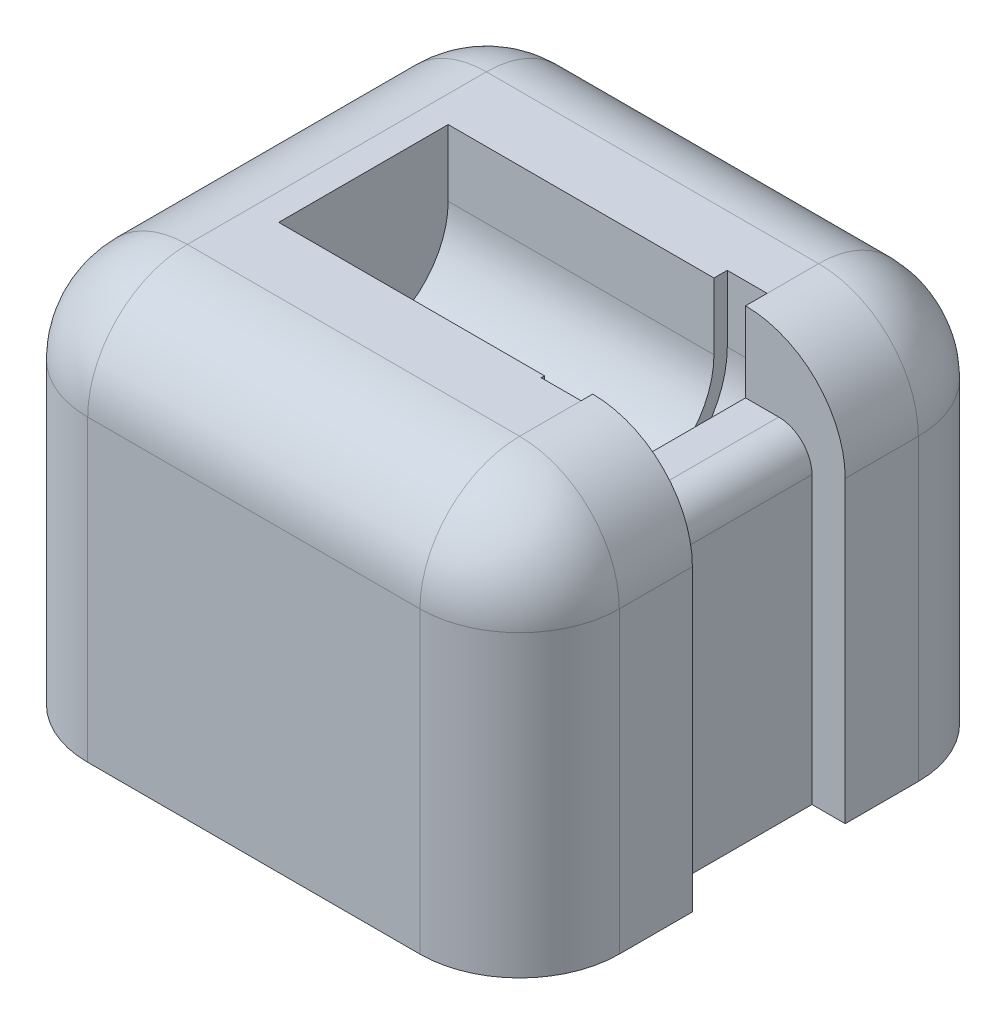
SolidWorks part; units mm, degrees
ref_plane "Front Plane" through (0, 0, 0) normal (0, 0, 1) x (1, 0, 0)
ref_plane "Top Plane" through (0, 0, 0) normal (0, 1, 0) x (1, 0, 0)
ref_plane "Right Plane" through (0, 0, 0) normal (1, 0, 0) x (0, 0, -1)
sketch "Sketch1" plane through (0, 0, 0) normal (0, 1, 0) x (1, 0, 0)
  line L1 (7.5, -7.5) -> (-7.5, -7.5)
  line L2 (7.5, -7.5) -> (7.5, 7.5)
  line L3 (7.5, 7.5) -> (-7.5, 7.5)
  line L4 (-7.5, -7.5) -> (-7.5, 7.5)
  line L5 (7.5, -7.5) -> (-7.5, 7.5) construction
  line L6 (7.5, 7.5) -> (-7.5, -7.5) construction
  point P0 (0, 0)
  dimension "D1" = 15
  dimension "D2" = 15
extrude "Boss-Extrude1" add sketch "Sketch1" along normal blind 12
sketch "Sketch2" plane through (7.5, 0, 0) normal (1, 0, 0) x (0, 0, -1)
  line L2 (2.3, 10.4) -> (2.3, 9.6)
  line L3 (2.3, 9.6) -> (-2.3, 9.6)
  line L4 (-2.3, 10.4) -> (-2.3, 9.6)
  line L5 (2.3, 10.4) -> (-2.3, 9.6) construction
  line L6 (2.3, 9.6) -> (-2.3, 10.4) construction
  line L7 (-7.5, 12) -> (7.5, 12) construction
  line L9 (-2.3, 10.4) -> (-2.3, 12)
  line L10 (-2.3, 12) -> (2.3, 12)
  line L11 (2.3, 10.4) -> (2.3, 12)
  point P0 (0, 10)
  point P9 (-1.3001, 10.2334)
  point P11 (2.1985, 10.3824)
  point P14 (0, 10)
  point P15 (-2.4019, 9.6178)
  point P16 (0, 0)
  dimension "D1" = 10
  dimension "D2" = 0.8
  dimension "D3" = 4.6
extrude "Cut-Extrude1" cut sketch "Sketch2" against normal blind 2
sketch "Sketch3" plane through (5.5, 0, 0) normal (1, 0, 0) x (0, 0, -1)
  line L0 (-2.65, 11.2961) -> (-2.65, 8.7039)
  line L1 (-2.65, 10) -> (2.95, 10) construction
  line L2 (-2.65, 11.2961) -> (-2.65, 12)
  line L3 (-7.5, 12) -> (-2.3, 12) construction
  line L4 (-2.65, 12) -> (2.95, 12)
  line L5 (2.95, 12) -> (2.95, 10)
  arc A0 (-2.65, 8.7039) -> (2.95, 10) centre (0, 10) ccw
  dimension "D1" = 5.9
  dimension "D2" = 5.6
extrude "Cut-Extrude2" cut sketch "Sketch3" against normal blind 1.2
sketch "Sketch4" plane through (4.3, 0, 0) normal (1, 0, 0) x (0, 0, -1)
  line L0 (-2.55, 10) -> (-2.55, 12)
  line L1 (2.95, 12) -> (-2.65, 12) construction
  line L2 (-2.55, 12) -> (2.55, 12)
  line L3 (2.55, 12) -> (2.55, 10)
  arc A0 (-2.55, 10) -> (2.55, 10) centre (0, 10) ccw
  dimension "D1" = 5.1
extrude "Cut-Extrude3" cut sketch "Sketch4" against normal blind 8
sketch "Sketch5" plane through (7.5, 0, 0) normal (1, 0, 0) x (0, 0, -1)
  line L0 (2.3, 0) -> (7.5, 0)
  line L8 (2.3, 9.6) -> (-2.3, 9.6)
  line L9 (-2.3, 9.6) -> (-2.3, 12)
  line L10 (-2.3, 12) -> (-7.5, 12)
  line L11 (-7.5, 12) -> (-7.5, 0)
  line L12 (-7.5, 0) -> (7.5, 0)
  line L13 (7.5, 0) -> (7.5, 12)
  line L14 (7.5, 12) -> (2.3, 12)
  line L15 (2.3, 12) -> (2.3, 9.6)
  line L17 (-2.3, 0) -> (-2.3, 12)
  line L18 (-2.3, 12) -> (-7.5, 12)
  line L19 (-7.5, 12) -> (-7.5, 0)
  line L20 (-7.5, 0) -> (-2.3, 0)
  line L21 (7.5, 0) -> (7.5, 12)
  line L22 (7.5, 12) -> (2.3, 12)
  line L23 (2.3, 12) -> (2.3, 0)
  dimension "D1" = 0
extrude "Boss-Extrude2" add sketch "Sketch5" along normal blind 1
fillet "Fillet2" radius 1 1 edges at (7.5, 9.6, 0)
fillet "Fillet3" radius 3 7 edges at (0.5, 12, 7.5) (-7.5, 12, 0) (0.5, 12, -7.5) (-7.5, 6, -7.5) (-7.5, 6, 7.5) (8.5, 6, 7.5) (8.5, 6, -7.5)
fillet "Fillet4" radius 3 4 edges at (8.5, 12, 3.4) (8.5, 12, -3.4) (7.6213, 11.1213, 6.6213) (7.6213, 11.1213, -6.6213)
